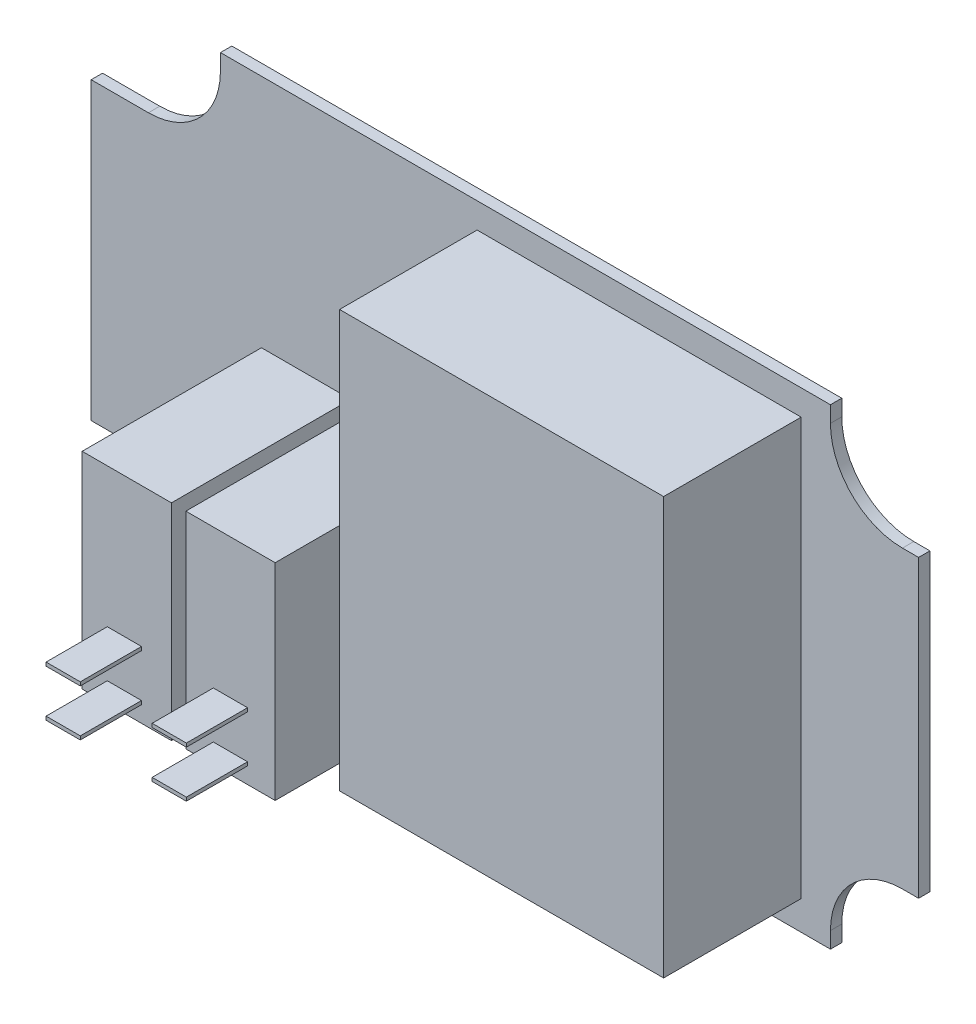
SolidWorks part; units mm, degrees
ref_plane "Front Plane" through (0, 0, 0) normal (0, 0, 1) x (1, 0, 0)
ref_plane "Top Plane" through (0, 0, 0) normal (0, 1, 0) x (1, 0, 0)
ref_plane "Right Plane" through (0, 0, 0) normal (1, 0, 0) x (0, 0, -1)
sketch "Sketch1" plane through (0, 0, 0) normal (0, 0, 1) x (1, 0, 0)
  line L0 (-42.3541, 30.2967) -> (-52.3541, 30.2967) construction
  line L1 (42.3541, -30.7033) -> (42.3541, -32.9433)
  line L2 (-52.3541, -20.7033) -> (-60.3013, -20.7033)
  line L4 (52.3541, -20.7033) -> (54.5933, -20.7033)
  line L5 (-52.3541, 30.2967) -> (-52.3541, 20.2967) construction
  line L6 (-52.3541, -20.7033) -> (-52.3541, -30.7033) construction
  line L7 (-52.3541, -30.7033) -> (-42.3541, -30.7033) construction
  line L8 (42.3541, -30.7033) -> (52.3541, -30.7033) construction
  line L9 (52.3541, -30.7033) -> (52.3541, -20.7033) construction
  line L10 (52.3541, 20.2967) -> (52.3541, 30.2967) construction
  line L11 (52.3541, 30.2967) -> (42.3541, 30.2967) construction
  line L12 (54.5933, -20.7033) -> (54.5933, 20.2967)
  line L13 (-60.3013, -20.7033) -> (-60.3013, 20.2967)
  line L14 (-60.3013, 20.2967) -> (-52.3541, 20.2967)
  line L15 (54.5933, 20.2967) -> (52.3541, 20.2967)
  line L16 (42.3541, -32.9433) -> (-42.3541, -32.9433)
  line L17 (-42.3541, -32.9433) -> (-42.3541, -30.7033)
  line L21 (0, -32.9433) -> (0, 0) construction
  line L24 (42.3541, 30.2967) -> (42.3541, 32.5367)
  line L25 (42.3541, 32.5367) -> (-42.3541, 32.5367)
  line L26 (-42.3541, 32.5367) -> (-42.3541, 30.2967)
  arc A0 (-42.3541, 30.2967) -> (-52.3541, 20.2967) centre (-52.3541, 30.2967) cw
  arc A2 (-52.3541, -20.7033) -> (-42.3541, -30.7033) centre (-52.3541, -30.7033) cw
  arc A4 (42.3541, 30.2967) -> (52.3541, 20.2967) centre (52.3541, 30.2967) ccw
  arc A5 (52.3541, -20.7033) -> (42.3541, -30.7033) centre (52.3541, -30.7033) ccw
  dimension "D1" = 41
  dimension "D3" = 10
  dimension "D5" = 84.7082
  dimension "D6" = 2.24
  dimension "D7" = 7.9472
  dimension "D8" = 2.2392
extrude "Boss-Extrude1" add sketch "Sketch1" along normal blind 1.5748
sketch "Sketch2" plane through (0, 0, 1.5748) normal (0, 0, 1) x (1, 0, 0)
  line L1 (-36.6572, -0.1162) -> (-24.2572, -0.1162)
  line L2 (-36.6572, -0.1162) -> (-36.6572, -28.7162)
  line L3 (-36.6572, -28.7162) -> (-24.2572, -28.7162)
  line L4 (-24.2572, -0.1162) -> (-24.2572, -28.7162)
  line L5 (-22.2572, -0.1162) -> (-9.8572, -0.1162)
  line L6 (-22.2572, -0.1162) -> (-22.2572, -28.7162)
  line L7 (-22.2572, -28.7162) -> (-9.8572, -28.7162)
  line L8 (-9.8572, -0.1162) -> (-9.8572, -28.7162)
  dimension "D1" = 2
  dimension "D2" = 28.6
  dimension "D3" = 12.4
extrude "Boss-Extrude2" add sketch "Sketch2" along normal blind 24.9
sketch "Sketch3" plane through (0, 0, 26.4748) normal (0, 0, 1) x (1, 0, 0)
  line L1 (-13.6892, -26.4707) -> (-18.4392, -26.4707)
  line L2 (-13.6892, -26.4707) -> (-13.6892, -25.9707)
  line L3 (-13.6892, -25.9707) -> (-18.4392, -25.9707)
  line L4 (-18.4392, -26.4707) -> (-18.4392, -25.9707)
  line L5 (-13.6892, -19.9707) -> (-18.4392, -19.9707)
  line L6 (-13.6892, -19.9707) -> (-13.6892, -19.4707)
  line L7 (-13.6892, -19.4707) -> (-18.4392, -19.4707)
  line L8 (-18.4392, -19.9707) -> (-18.4392, -19.4707)
  line L9 (-28.4177, -26.4707) -> (-33.1677, -26.4707)
  line L10 (-28.4177, -26.4707) -> (-28.4177, -25.9707)
  line L11 (-28.4177, -25.9707) -> (-33.1677, -25.9707)
  line L12 (-33.1677, -26.4707) -> (-33.1677, -25.9707)
  line L13 (-28.4177, -19.9707) -> (-33.1677, -19.9707)
  line L14 (-28.4177, -19.9707) -> (-28.4177, -19.4707)
  line L15 (-28.4177, -19.4707) -> (-33.1677, -19.4707)
  line L16 (-33.1677, -19.9707) -> (-33.1677, -19.4707)
  dimension "D1" = 0.5
  dimension "D2" = 4.75
  dimension "D3" = 6
extrude "Boss-Extrude3" add sketch "Sketch3" along normal blind 8.5
sketch "Sketch4" plane through (0, 0, 1.5748) normal (0, 0, 1) x (1, 0, 0)
  line L1 (38.2866, -28.8884) -> (-6.7134, -28.8884)
  line L2 (38.2866, -28.8884) -> (38.2866, 29.0116)
  line L3 (38.2866, 29.0116) -> (-6.7134, 29.0116)
  line L4 (-6.7134, -28.8884) -> (-6.7134, 29.0116)
  dimension "D1" = 57.9
  dimension "D2" = 45
extrude "Boss-Extrude4" add sketch "Sketch4" along normal blind 19.1
